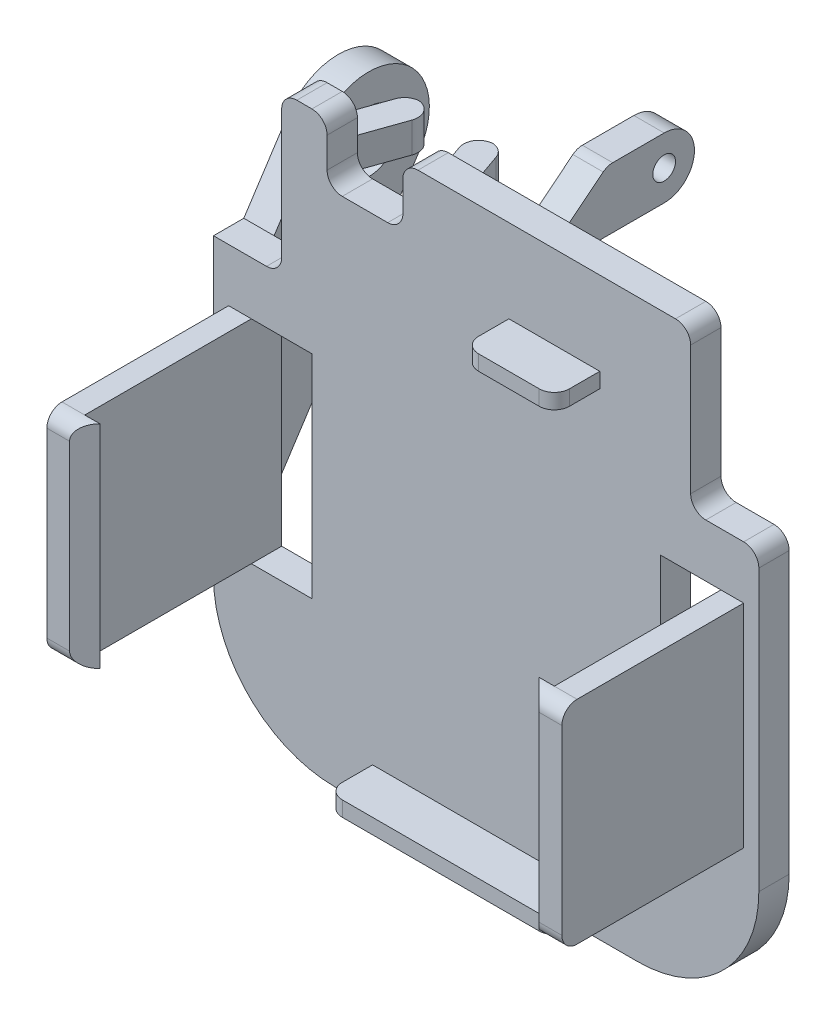
SolidWorks part; units mm, degrees
ref_plane "前视基准面" through (0, 0, 0) normal (0, 0, 1) x (1, 0, 0)
ref_plane "上视基准面" through (0, 0, 0) normal (0, 1, 0) x (1, 0, 0)
ref_plane "右视基准面" through (0, 0, 0) normal (1, 0, 0) x (0, 0, -1)
sketch "草图1" plane through (0, 0, 0) normal (0, 0, 1) x (1, 0, 0)
  line L1 (-18, 19) -> (18, 19)
  line L2 (-18, 19) -> (-18, -19)
  line L3 (-18, -19) -> (18, -19)
  line L4 (18, 19) -> (18, -19)
  line L5 (-18, 19) -> (18, -19) construction
  line L6 (-18, -19) -> (18, 19) construction
  point P0 (0, 0)
  dimension "D1" = 38
  dimension "D2" = 36
extrude "凸台-拉伸1" add sketch "草图1" along normal blind 2
sketch "草图2" plane through (0, 0, 2) normal (0, 0, 1) x (1, 0, 0)
  line L0 (18, 19) -> (-18, 19) construction
  line L1 (11.5, 5) -> (15.5, 5)
  line L2 (11.5, 5) -> (11.5, -9)
  line L3 (11.5, -9) -> (15.5, -9)
  line L4 (15.5, 5) -> (15.5, -9)
  line L5 (11.5, 5) -> (15.5, -9) construction
  line L6 (11.5, -9) -> (15.5, 5) construction
  line L7 (-18, -19) -> (18, -19) construction
  line L8 (18, -19) -> (18, 19) construction
  line L9 (13.5, 5) -> (13.5, 19) construction
  line L10 (18, 19) -> (13.5, 19)
  line L11 (18, 19) -> (18, 8.5)
  line L12 (18, 8.5) -> (13.5, 8.5)
  line L13 (13.5, 19) -> (13.5, 8.5)
  line L15 (15.5, 5) -> (17, 5)
  line L16 (15.5, 5) -> (15.5, -9)
  line L17 (15.5, -9) -> (17, -9)
  line L18 (17, 5) -> (17, -9)
  point P0 (13.5, -2)
  dimension "D1" = 14
  dimension "D2" = 10
  dimension "D3" = 4
  dimension "D4" = 2.5
  dimension "D5" = 3.5
  dimension "D6" = 1.5
extrude "切除-拉伸1" cut sketch "草图2" against normal up to next contours L4 L1 L2 L3 | L12 L13 L10 L11 region at (13.5, -2, 2)
extrude "凸台-拉伸2" add sketch "草图2<3>" along normal blind 12 contours L18 L15 L4 L17 region at (16.25, -2, 2)
sketch "草图2<3>" plane through (0, 0, 2) normal (0, 0, 1) x (1, 0, 0) same geometry as "草图2"
sketch "草图3" plane through (0, 5, 0) normal (0, 1, 0) x (1, 0, 0)
  line L0 (15.5, -14) -> (14.5, -13)
  line L1 (14.5, -13) -> (15.5, -13)
  line L2 (15.5, -14) -> (15.5, -2) construction
  line L3 (15.5, -13) -> (15.5, -14)
  dimension "D1" = 1
extrude "凸台-拉伸3" add sketch "草图3" against normal up to surface (14 mm away) up to face at (16.25, -9, 8)
mirror "镜向1" about plane through (0, 0, 0) normal (1, 0, 0) of "凸台-拉伸2", "切除-拉伸1", "凸台-拉伸3"
sketch "草图4" plane through (0, 0, 2) normal (0, 0, 1) x (1, 0, 0)
  line L0 (-18, -19) -> (18, -19) construction
  line L1 (-7.5, -16.5) -> (7.5, -16.5)
  line L2 (-7.5, -16.5) -> (-7.5, -17.5)
  line L3 (-7.5, -17.5) -> (7.5, -17.5)
  line L4 (7.5, -16.5) -> (7.5, -17.5)
  line L5 (0, -19) -> (0, -16.5) construction
  line L6 (-11.5, -2) -> (11.5, -2) construction
  line L7 (-11.5, 5) -> (-11.5, -9) construction
  line L8 (11.5, 5) -> (11.5, -9) construction
  line L9 (7.5, 12.5) -> (7.5, 13.5)
  line L10 (7.5, 13.5) -> (1.5, 13.5)
  line L11 (1.5, 13.5) -> (1.5, 12.5)
  line L12 (1.5, 12.5) -> (7.5, 12.5)
  dimension "D1" = 2.5
  dimension "D2" = 1
  dimension "D3" = 15
  dimension "D4" = 6
extrude "凸台-拉伸4" add sketch "草图4" along normal blind 3
sketch "草图5" plane through (0, 0, 2) normal (0, 0, 1) x (1, 0, 0)
  line L0 (13.5, 19) -> (-13.5, 19) construction
  line L1 (-10.5, 19) -> (-5.5, 19)
  line L2 (-10.5, 19) -> (-10.5, 15)
  line L3 (-10.5, 15) -> (-5.5, 15)
  line L4 (-5.5, 19) -> (-5.5, 15)
  line L5 (-13.5, 19) -> (-13.5, 8.5) construction
  dimension "D1" = 5
  dimension "D2" = 3
  dimension "D3" = 4
extrude "切除-拉伸2" cut sketch "草图5" against normal up to next
sketch "草图6" plane through (3.5, 0, 0) normal (1, 0, 0) x (0, 0, -1)
  line L1 (0, 8.5) -> (0, 19) construction
  line L2 (0, 19) -> (0, 15) construction
  line L3 (0, 19) -> (0, 17)
  line L4 (2.5, 21) -> (10, 21) construction
  line L5 (2.5, 21) -> (6.25, 21)
  line L6 (2.5, 21) -> (0, 19)
  line L7 (0, 17) -> (6.25, 17)
  line L8 (12.5, 5) -> (0.4992, 5) construction
  line L9 (12.5, -6) -> (12.5, 16) construction
  line L10 (6.25, -7) -> (0, -7)
  line L11 (0, -7) -> (0, -16)
  line L12 (0, -16) -> (7.4237, -10.6194)
  line L13 (0, -19) -> (0, 8.5) construction
  circle A0 centre (6.25, 19) radius 0.75
  arc A1 (6.25, 21) -> (6.25, 17) centre (6.25, 19) cw
  circle A2 centre (6.25, -9) radius 0.75
  arc A3 (6.25, -11) -> (6.25, -7) centre (6.25, -9) ccw
  dimension "D1" = 1.5
  dimension "D2" = 9
extrude "凸台-拉伸5" add sketch "草图6" against normal blind 2 contours A3 L12 L11 L10 A2 | A1 L7 L3 L6 L5 | A0 region at (3.5, -10.3528, -3.2397)
sketch "草图7" plane through (-18, 0, 0) normal (-1, 0, 0) x (0, 0, 1)
  line L0 (0, 8.5) -> (0, -19) construction
  line L1 (0, 8.5) -> (0, -19)
  line L2 (-2.902, 12.9388) -> (0, 8.5)
  line L3 (-9.598, 8.5612) -> (0, -6.1196)
  circle A0 centre (-6.25, 10.75) radius 2 construction
  circle A1 centre (-6.25, 10.75) radius 2
  arc A2 (-2.902, 12.9388) -> (-9.598, 8.5612) centre (-6.25, 10.75) ccw
  circle A3 centre (-6.25, 10.75) radius 4 construction
  line M5 (0, 8.5) -> (0, -19)
  dimension "D1" = 2
extrude "凸台-拉伸6" add sketch "草图7" against normal blind 2 contours L2 A2 L3 A1 M5 region at (-18, 6.1461, -3.9902)
sketch "草图8" plane through (0, 15, 0) normal (0, 1, 0) x (1, 0, 0)
  line L0 (-10.5, 0) -> (-12.5, 0)
  line L1 (-10.5, 0) -> (-13.5, 0) construction
  line L2 (-12.5, 0) -> (-11.0943, 4)
  line L3 (-11.0943, 4) -> (-9.0943, 4)
  line L4 (-9.0943, 4) -> (-10.5, 0)
  line L5 (-8, 0) -> (-8, 4) construction
  line L6 (-5.5, 0) -> (-10.5, 0) construction
  line L7 (-4.9057, 4) -> (-6.9057, 4)
  line L8 (-6.9057, 4) -> (-5.5, 0)
  line L9 (-5.5, 0) -> (-3.5, 0)
  line L10 (-3.5, 0) -> (-4.9057, 4)
  dimension "D1" = 2
  dimension "D2" = 4
extrude "凸台-拉伸7" add sketch "草图8" along normal blind 2
fillet "圆角1" radius 8 2 edges at (-18, -19, 1) (18, -19, 1)
fillet "圆角2" radius 1 24 edges at (16.25, -9, 14) (16.25, 5, 14) (-16.25, 5, 14) (-16.25, -9, 14) (-7.5, -17, 5) (7.5, -17, 5) (7.5, 13, 5) (1.5, 13, 5) (-13.5, 8.5, 1) (-13.5, 19, 1) (-10.5, 19, 1) (-12.5, 16, 0) (-3.5, 16, 0) (-4.9057, 16, -4) (-11.0943, 16, -4) (-9.0943, 16, -4) (-6.9057, 16, -4) (-10.5, 15, 1) (-5.5, 15, 1) (2.5, 21, -2.5) (-5.5, 19, 1) (18, 8.5, 1) (13.5, 8.5, 1) (13.5, 19, 1)
equation "\"1。5\"=1.24781"
